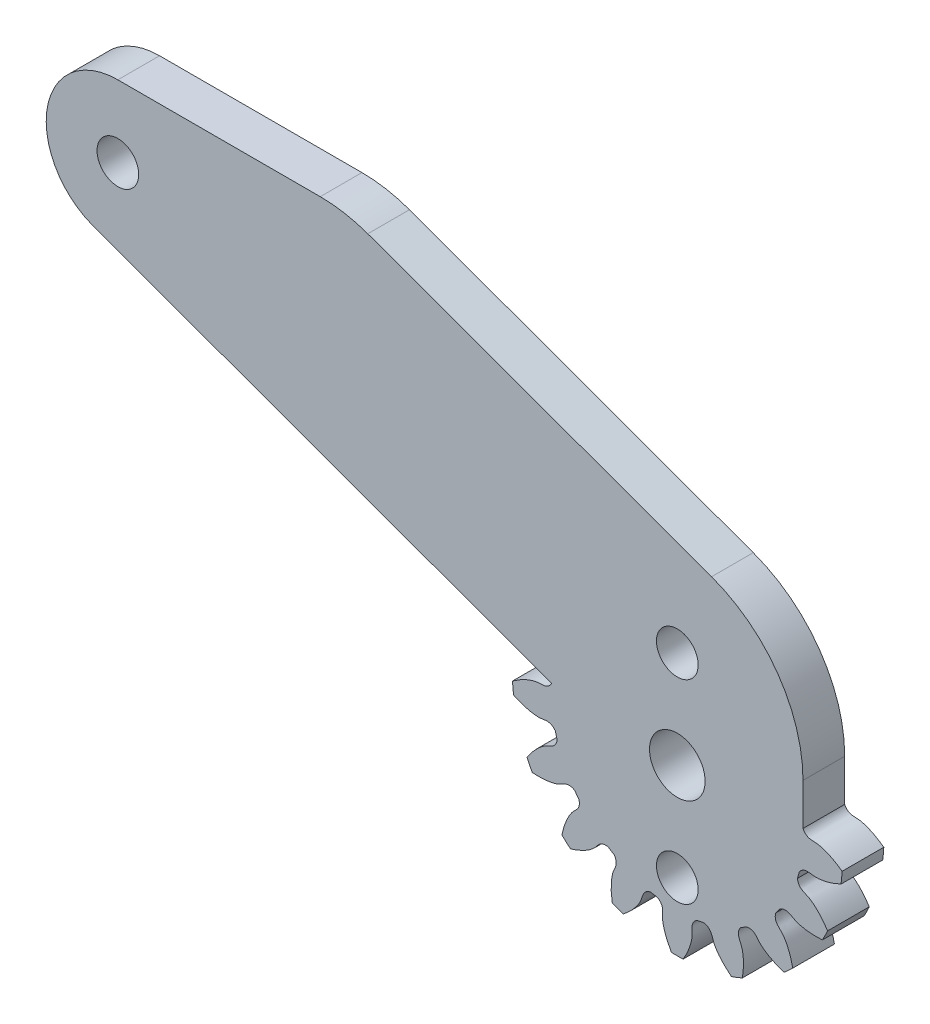
SolidWorks part; units mm, degrees
ref_plane "前视基准面" through (0, 0, 0) normal (0, 0, 1) x (1, 0, 0)
ref_plane "上视基准面" through (0, 0, 0) normal (0, 1, 0) x (1, 0, 0)
ref_plane "右视基准面" through (0, 0, 0) normal (1, 0, 0) x (0, 0, -1)
sketch "草图1" plane through (0, 0, 0) normal (0, 0, 1) x (1, 0, 0)
  circle A0 centre (0, 0) radius 11.875
extrude "凸台-拉伸1" add sketch "草图1" along normal blind 30
ref_axis "基准轴1" through (0, 0, -1.5) along (0, 0, 1)
sketch "草图2" plane through (0, 0, 0) normal (0, 0, 1) x (1, 0, 0)
  line L0 (0, 0) -> (0, 11.875) construction
  circle A0 centre (0, 0) radius 11.875 construction
  arc A1 (0.2521, 9.059) -> (-0.2521, 9.059) centre (0, 0) ccw
  arc A2 (3.8946, 13.4259) -> (-3.8946, 13.4259) centre (0, 0) ccw
  spline S0 degree 3 poles (0.2521, 9.059) (0.7848, 9.281) (0.7077, 9.6935) (0.7979, 10.081) (0.8062, 10.1139) (0.8163, 10.1505) (0.8282, 10.1907) (0.8421, 10.2345) (0.8582, 10.2818) (0.8766, 10.3324) (0.8974, 10.3865) (0.9208, 10.4438) (0.947, 10.5043) (0.976, 10.5679) (1.008, 10.6345) (1.0431, 10.704) (1.0815, 10.7763) (1.1232, 10.8513) (1.1685, 10.929) (1.2174, 11.0091) (1.27, 11.0916) (1.3265, 11.1763) (1.3869, 11.2632) (1.4514, 11.3521) (1.5201, 11.4429) (1.5931, 11.5354) (1.6704, 11.6295) (1.7522, 11.7251) (1.8386, 11.822) (1.9295, 11.9201) (2.0252, 12.0192) (2.1257, 12.1193) (2.2311, 12.22) (2.3414, 12.3213) (2.4567, 12.4231) (2.577, 12.5251) (2.7025, 12.6272) (2.8331, 12.7292) (2.969, 12.831) (3.1101, 12.9323) (3.2564, 13.0331) (3.4081, 13.1332) (3.6198, 13.2668) (3.7832, 13.3632) (3.8946, 13.4259) knots 0 0 0 0 0.193883 0.199024 0.204851 0.211363 0.21856 0.226443 0.235011 0.244265 0.254205 0.264829 0.27614 0.288136 0.300817 0.314184 0.328236 0.342973 0.358397 0.374505 0.391299 0.408779 0.426944 0.445795 0.465331 0.485552 0.506459 0.528051 0.550329 0.573293 0.596941 0.621276 0.646296 0.672001 0.698392 0.725468 0.753229 0.781677 0.810809 0.840627 0.871131 0.90232 0.934195 1 1 1 1
  spline S1 degree 3 poles (-0.2521, 9.059) (-0.7848, 9.281) (-0.7077, 9.6935) (-0.7979, 10.081) (-0.8062, 10.1139) (-0.8163, 10.1505) (-0.8282, 10.1907) (-0.8421, 10.2345) (-0.8582, 10.2818) (-0.8766, 10.3324) (-0.8974, 10.3865) (-0.9208, 10.4438) (-0.947, 10.5043) (-0.976, 10.5679) (-1.008, 10.6345) (-1.0431, 10.704) (-1.0815, 10.7763) (-1.1232, 10.8513) (-1.1685, 10.929) (-1.2174, 11.0091) (-1.27, 11.0916) (-1.3265, 11.1763) (-1.3869, 11.2632) (-1.4514, 11.3521) (-1.5201, 11.4429) (-1.5931, 11.5354) (-1.6704, 11.6295) (-1.7522, 11.7251) (-1.8386, 11.822) (-1.9295, 11.9201) (-2.0252, 12.0192) (-2.1257, 12.1193) (-2.2311, 12.22) (-2.3414, 12.3213) (-2.4567, 12.4231) (-2.577, 12.5251) (-2.7025, 12.6272) (-2.8331, 12.7292) (-2.969, 12.831) (-3.1101, 12.9323) (-3.2564, 13.0331) (-3.4081, 13.1332) (-3.6198, 13.2668) (-3.7832, 13.3632) (-3.8946, 13.4259) knots 0 0 0 0 0.193883 0.199024 0.204851 0.211363 0.21856 0.226443 0.235011 0.244265 0.254205 0.264829 0.27614 0.288136 0.300817 0.314184 0.328236 0.342973 0.358397 0.374505 0.391299 0.408779 0.426944 0.445795 0.465331 0.485552 0.506459 0.528051 0.550329 0.573293 0.596941 0.621276 0.646296 0.672001 0.698392 0.725468 0.753229 0.781677 0.810809 0.840627 0.871131 0.90232 0.934195 1 1 1 1
extrude "切除-拉伸1" cut sketch "草图2" along normal through all
pattern_circular "阵列(圆周)1" count 17 every 21.176 about axis through (0, 0, -1.5) along (0, 0, 1) of "切除-拉伸1"
sketch "草图3" plane through (0, 0, 0) normal (0, 0, 1) x (1, 0, 0)
  circle A0 centre (0, 0) radius 10.625 construction
  dimension "Dn" = 21.25
sketch "草图4" plane through (0, 0, 0) normal (0, 1, 0) x (1, 0, 0)
  line L1 (-14.2819, 27) -> (14.2819, 27)
  line L2 (-14.2819, 27) -> (-14.2819, -27)
  line L3 (-14.2819, -27) -> (14.2819, -27)
  line L4 (14.2819, 27) -> (14.2819, -27)
  line L5 (-14.2819, 27) -> (14.2819, -27) construction
  line L6 (-14.2819, -27) -> (14.2819, 27) construction
  point P0 (0, 0)
  dimension "D1" = 3
extrude "切除-拉伸2" cut sketch "草图4" against normal through all both and the other way through all
sketch "草图5" plane through (0, 0, 30) normal (0, 0, 1) x (1, 0, 0)
  arc A0 (8.9971, 1.0869) -> (-8.9971, 1.0869) centre (0, 0) ccw
  arc A34 (-3.0374, 8.5383) -> (-3.5076, 8.3562) centre (0, 0) ccw
  arc A35 (-5.8907, 10.3109) -> (-6.6043, 9.8691) centre (0, 0) ccw
  arc A36 (-5.9167, 6.8645) -> (-6.2893, 6.5248) centre (0, 0) ccw
  arc A37 (-9.2176, 7.4867) -> (-9.7234, 6.8169) centre (0, 0) ccw
  arc A38 (-7.9969, 4.2636) -> (-8.2217, 3.8123) centre (0, 0) ccw
  arc A39 (-11.2997, 3.6513) -> (-11.5294, 2.8441) centre (0, 0) ccw
  arc A40 (-8.9971, 1.0869) -> (-9.0436, 0.5848) centre (0, 0) ccw
  arc A41 (-11.8557, -0.6771) -> (-11.7782, -1.5129) centre (0, 0) ccw
  arc A42 (-8.7822, -2.2366) -> (-8.6442, -2.7216) centre (0, 0) ccw
  arc A43 (-10.8105, -4.9142) -> (-10.4364, -5.6655) centre (0, 0) ccw
  arc A44 (-7.3812, -5.2581) -> (-7.0773, -5.6605) centre (0, 0) ccw
  arc A45 (-8.3053, -8.4875) -> (-7.685, -9.053) centre (0, 0) ccw
  arc A46 (-4.9833, -7.5694) -> (-4.5546, -7.8348) centre (0, 0) ccw
  arc A47 (-4.6784, -10.9146) -> (-3.8958, -11.2178) centre (0, 0) ccw
  arc A48 (-1.9124, -8.8584) -> (-1.4168, -8.9511) centre (0, 0) ccw
  arc A49 (-0.4197, -11.8676) -> (0.4197, -11.8676) centre (0, 0) ccw
  arc A50 (1.4168, -8.9511) -> (1.9124, -8.8584) centre (0, 0) ccw
  arc A51 (3.8958, -11.2178) -> (4.6784, -10.9146) centre (0, 0) ccw
  arc A52 (4.5546, -7.8348) -> (4.9833, -7.5694) centre (0, 0) ccw
  arc A53 (7.685, -9.053) -> (8.3053, -8.4875) centre (0, 0) ccw
  arc A54 (7.0773, -5.6605) -> (7.3812, -5.2581) centre (0, 0) ccw
  arc A55 (10.4364, -5.6655) -> (10.8105, -4.9142) centre (0, 0) ccw
  arc A56 (8.6442, -2.7216) -> (8.7822, -2.2366) centre (0, 0) ccw
  arc A57 (11.7782, -1.5129) -> (11.8557, -0.6771) centre (0, 0) ccw
  arc A58 (9.0436, 0.5848) -> (8.9971, 1.0869) centre (0, 0) ccw
  arc A59 (11.5294, 2.8441) -> (11.2997, 3.6513) centre (0, 0) ccw
  arc A60 (8.2217, 3.8123) -> (7.9969, 4.2636) centre (0, 0) ccw
  arc A61 (9.7234, 6.8169) -> (9.2176, 7.4867) centre (0, 0) ccw
  arc A62 (6.2893, 6.5248) -> (5.9167, 6.8645) centre (0, 0) ccw
  arc A63 (6.6043, 9.8691) -> (5.8907, 10.3109) centre (0, 0) ccw
  arc A64 (3.5076, 8.3562) -> (3.0374, 8.5383) centre (0, 0) ccw
  arc A65 (2.5932, 11.5884) -> (1.7682, 11.7426) centre (0, 0) ccw
  arc A66 (0.2521, 9.059) -> (-0.2521, 9.059) centre (0, 0) ccw
  arc A67 (-1.7682, 11.7426) -> (-2.5932, 11.5884) centre (0, 0) ccw
  arc A68 (-3.0374, 8.5383) -> (-3.5076, 8.3562) centre (0, 0) ccw
  arc A69 (-5.8907, 10.3109) -> (-6.6043, 9.8691) centre (0, 0) ccw
  arc A70 (-5.9167, 6.8645) -> (-6.2893, 6.5248) centre (0, 0) ccw
  arc A71 (-9.2176, 7.4867) -> (-9.7234, 6.8169) centre (0, 0) ccw
  arc A72 (-7.9969, 4.2636) -> (-8.2217, 3.8123) centre (0, 0) ccw
  arc A73 (-11.2997, 3.6513) -> (-11.5294, 2.8441) centre (0, 0) ccw
  arc A93 (11.5294, 2.8441) -> (11.2997, 3.6513) centre (0, 0) ccw
  arc A94 (8.2217, 3.8123) -> (7.9969, 4.2636) centre (0, 0) ccw
  arc A95 (9.7234, 6.8169) -> (9.2176, 7.4867) centre (0, 0) ccw
  arc A96 (6.2893, 6.5248) -> (5.9167, 6.8645) centre (0, 0) ccw
  arc A97 (6.6043, 9.8691) -> (5.8907, 10.3109) centre (0, 0) ccw
  arc A98 (3.5076, 8.3562) -> (3.0374, 8.5383) centre (0, 0) ccw
  arc A99 (2.5932, 11.5884) -> (1.7682, 11.7426) centre (0, 0) ccw
  arc A100 (0.2521, 9.059) -> (-0.2521, 9.059) centre (0, 0) ccw
  arc A101 (-1.7682, 11.7426) -> (-2.5932, 11.5884) centre (0, 0) ccw
  spline S34 degree 3 poles (3204.5235, 2397.2936) (-37.2918, -28.382) (-0.6945, 3.695) (-4.3928, 9.1225) (-4.43, 9.1736) (-4.4845, 9.2426) (-4.5521, 9.3214) (-4.6337, 9.4092) (-4.73, 9.505) (-4.8419, 9.6076) (-4.9699, 9.716) (-5.1147, 9.8291) (-5.277, 9.9456) (-5.4571, 10.0643) (-28.9545, 24.2415) (-145.9515, -123.9226) (3580.2885, 1781.0225) knots -2.702617 -2.702617 -2.702617 -2.702617 0.661536 0.666677 0.679016 0.694096 0.711918 0.732483 0.755789 0.781837 0.810627 0.842158 0.876432 0.913448 0.953205 15.004551 15.004551 15.004551 15.004551 only from (-3.5076, 8.3562) to (-5.8907, 10.3109)
  spline S35 degree 3 poles (-3190.1071, -2411.2489) (175.7802, 75.3751) (-8.7927, 36.7085) (-6.5767, 9.371) (-6.5507, 9.1569) (-6.5188, 8.9597) (-6.4821, 8.7797) (-6.4422, 8.6167) (-6.4001, 8.4709) (-6.3574, 8.342) (-6.3151, 8.2298) (-6.2747, 8.1342) (-6.2373, 8.0546) (-6.2081, 7.9985) (-2.9981, 2.2687) (42.0277, 20.7308) (-3574.1983, -1799.9306) knots -13.996313 -13.996313 -13.996313 -13.996313 0.046795 0.086552 0.123568 0.157842 0.189373 0.218163 0.244211 0.267517 0.288082 0.305904 0.320984 0.333323 0.338464 3.702571 3.702571 3.702571 3.702571 only from (-6.6043, 9.8691) to (-5.9167, 6.8645)
  spline S36 degree 3 poles (2122.1269, 3393.0171) (-24.5208, -39.9368) (-1.9823, 3.1946) (-7.3916, 6.9196) (-7.4448, 6.9538) (-7.5205, 6.9984) (-7.612, 7.0475) (-7.7198, 7.0999) (-7.8442, 7.1544) (-7.9856, 7.2097) (-8.1441, 7.2646) (-8.32, 7.3177) (-8.5134, 7.3677) (-8.7242, 7.4133) (-35.7563, 12.145) (-91.3297, -168.2782) (2695.1401, 2954.1034) knots -2.702617 -2.702617 -2.702617 -2.702617 0.661536 0.666677 0.679016 0.694096 0.711918 0.732483 0.755789 0.781837 0.810627 0.842158 0.876432 0.913448 0.953205 15.004551 15.004551 15.004551 15.004551 only from (-6.2893, 6.5248) to (-9.2176, 7.4867)
  spline S37 degree 3 poles (-2103.6427, -3400.8222) (136.6815, 133.7844) (-21.4596, 31.0533) (-9.5178, 6.3624) (-9.4162, 6.1721) (-9.3152, 5.9998) (-9.216, 5.8452) (-9.1199, 5.7077) (-9.028, 5.5869) (-8.9415, 5.4821) (-8.8616, 5.3928) (-8.7894, 5.3182) (-8.7257, 5.2576) (-8.6783, 5.2158) (-3.6152, 1.0325) (31.7008, 34.5131) (-2682.6307, -2969.5347) knots -13.996313 -13.996313 -13.996313 -13.996313 0.046795 0.086552 0.123568 0.157842 0.189373 0.218163 0.244211 0.267517 0.288082 0.305904 0.320984 0.333323 0.338464 3.702571 3.702571 3.702571 3.702571 only from (-9.7234, 6.8169) to (-7.9969, 4.2636)
  spline S38 degree 3 poles (753.1252, 3930.4949) (-8.4382, -46.0979) (-3.0025, 2.2628) (-9.3921, 3.7822) (-9.4541, 3.7949) (-9.5408, 3.8091) (-9.6439, 3.8218) (-9.7633, 3.8318) (-9.899, 3.8377) (-10.0508, 3.8382) (-10.2184, 3.832) (-10.4016, 3.818) (-10.6, 3.7948) (-10.8131, 3.7612) (-37.7291, -1.5918) (-24.3733, -189.9068) (1445.998, 3728.2163) knots -2.702617 -2.702617 -2.702617 -2.702617 0.661536 0.666677 0.679016 0.694096 0.711918 0.732483 0.755789 0.781837 0.810627 0.842158 0.876432 0.913448 0.953205 15.004551 15.004551 15.004551 15.004551 only from (-8.2217, 3.8123) to (-11.2997, 3.6513)
  spline S39 degree 3 poles (-733.0697, -3931.0957) (79.1232, 174.1253) (-31.2282, 21.2042) (-11.1735, 2.4945) (-11.01, 2.3538) (-10.8536, 2.2296) (-10.7052, 2.1213) (-10.5659, 2.0278) (-10.4365, 1.9483) (-10.3181, 1.8819) (-10.2113, 1.8274) (-10.117, 1.784) (-10.0358, 1.7504) (-9.9764, 1.7286) (-3.7441, -0.3432) (17.0926, 43.6341) (-1428.759, -3738.0866) knots -13.996313 -13.996313 -13.996313 -13.996313 0.046795 0.086552 0.123568 0.157842 0.189373 0.218163 0.244211 0.267517 0.288082 0.305904 0.320984 0.333323 0.338464 3.702571 3.702571 3.702571 3.702571 only from (-11.5294, 2.8441) to (-8.9971, 1.0869)
  spline S40 degree 3 poles (-180.8455, 985.7124) (0.5211, -18.0724) (-5.9831, 0.7012) (-10.1242, 0.134) (-10.1865, 0.1234) (-10.2725, 0.1054) (-10.3733, 0.08) (-10.4882, 0.0461) (-10.6168, 0.0026) (-10.7586, -0.0518) (-10.9127, -0.1181) (-11.0784, -0.1973) (-11.255, -0.2906) (-11.4416, -0.3989) (-26.4837, -9.954) (2.0889, -85.1042) (11.954, 999.039) knots -1.473067 -1.473067 -1.473067 -1.473067 0.661536 0.666677 0.679016 0.694096 0.711918 0.732483 0.755789 0.781837 0.810627 0.842158 0.876432 0.913448 0.953205 10.050586 10.050586 10.050586 10.050586 only from (-9.0436, 0.5848) to (-11.8557, -0.6771)
  spline S41 degree 3 poles (195.3333, -979.8293) (-13.603, 83.9465) (-27.8517, 4.9141) (-11.3201, -1.7102) (-11.1168, -1.7824) (-10.9261, -1.8417) (-10.7486, -1.8891) (-10.5849, -1.926) (-10.4356, -1.9534) (-10.3011, -1.9725) (-10.1819, -1.9847) (-10.0783, -1.9911) (-9.9904, -1.9931) (-9.9272, -1.992) (-5.7524, -1.7887) (-2.8087, 17.8598) (3.3576, -1002.1119) knots -9.044973 -9.044973 -9.044973 -9.044973 0.046795 0.086552 0.123568 0.157842 0.189373 0.218163 0.244211 0.267517 0.288082 0.305904 0.320984 0.333323 0.338464 2.473034 2.473034 2.473034 2.473034 only from (-11.7782, -1.5129) to (-8.7822, -2.2366)
  spline S42 degree 3 poles (-524.7138, 853.8205) (7.0144, -16.6638) (-5.8324, -1.5074) (-9.4889, -3.5324) (-9.5433, -3.5647) (-9.6169, -3.6126) (-9.7017, -3.6727) (-9.7966, -3.7458) (-9.9008, -3.8328) (-10.0134, -3.9347) (-10.1331, -4.0522) (-10.2591, -4.186) (-10.39, -4.3368) (-10.5249, -4.5052) (-21.0995, -18.8488) (32.691, -78.6027) (-349.7478, 935.8944) knots -1.473067 -1.473067 -1.473067 -1.473067 0.661536 0.666677 0.679016 0.694096 0.711918 0.732483 0.755789 0.781837 0.810627 0.842158 0.876432 0.913448 0.953205 10.050586 10.050586 10.050586 10.050586 only from (-8.6442, -2.7216) to (-10.8105, -4.9142)
  spline S43 degree 3 poles (536.0981, -843.1011) (-43.0094, 73.3638) (-27.7461, -5.479) (-9.9378, -5.684) (-9.7222, -5.6779) (-9.523, -5.6643) (-9.3403, -5.6444) (-9.1744, -5.6196) (-9.0253, -5.5912) (-8.893, -5.5605) (-8.7774, -5.5288) (-8.6784, -5.4974) (-8.5958, -5.4675) (-8.5372, -5.4436) (-4.7178, -3.7459) (-9.0707, 15.6392) (365.1354, -933.2286) knots -9.044973 -9.044973 -9.044973 -9.044973 0.046795 0.086552 0.123568 0.157842 0.189373 0.218163 0.244211 0.267517 0.288082 0.305904 0.320984 0.333323 0.338464 2.473034 2.473034 2.473034 2.473034 only from (-10.4364, -5.6655) to (-7.3812, -5.2581)
  spline S44 degree 3 poles (-797.7166, 606.6154) (12.5604, -13.0046) (-4.894, -3.5126) (-7.5721, -6.7216) (-7.6111, -6.7714) (-7.6625, -6.8427) (-7.7198, -6.9293) (-7.7819, -7.0318) (-7.8477, -7.1506) (-7.9158, -7.2863) (-7.985, -7.4391) (-8.0541, -7.6093) (-8.1218, -7.7973) (-8.1867, -8.003) (-12.8657, -25.198) (58.878, -61.4855) (-664.2141, 746.3521) knots -1.473067 -1.473067 -1.473067 -1.473067 0.661536 0.666677 0.679016 0.694096 0.711918 0.732483 0.755789 0.781837 0.810627 0.842158 0.876432 0.913448 0.953205 10.050586 10.050586 10.050586 10.050586 only from (-7.0773, -5.6605) to (-8.3053, -8.4875)
  spline S45 degree 3 poles (804.4598, -592.5074) (-66.6071, 52.8729) (-23.8932, -15.132) (-7.2135, -8.8902) (-7.0146, -8.8066) (-6.8337, -8.7219) (-6.6706, -8.6374) (-6.5248, -8.5543) (-6.396, -8.474) (-6.2837, -8.3976) (-6.1874, -8.3262) (-6.1065, -8.2612) (-6.0403, -8.2034) (-5.9943, -8.16) (-3.0461, -5.1973) (-14.1077, 11.3064) (677.5997, -738.3076) knots -9.044973 -9.044973 -9.044973 -9.044973 0.046795 0.086552 0.123568 0.157842 0.189373 0.218163 0.244211 0.267517 0.288082 0.305904 0.320984 0.333323 0.338464 2.473034 2.473034 2.473034 2.473034 only from (-7.685, -9.053) to (-4.9833, -7.5694)
  spline S46 degree 3 poles (-962.9834, 277.4835) (16.41, -7.5891) (-3.2946, -5.0433) (-4.6327, -9.0031) (-4.651, -9.0636) (-4.6732, -9.1486) (-4.6954, -9.2501) (-4.7163, -9.3681) (-4.7346, -9.5027) (-4.7492, -9.6538) (-4.7585, -9.8213) (-4.7614, -10.005) (-4.7566, -10.2046) (-4.7428, -10.4199) (-2.8943, -28.1441) (77.1132, -36.0643) (-888.9747, 456.0108) knots -1.473067 -1.473067 -1.473067 -1.473067 0.661536 0.666677 0.679016 0.694096 0.711918 0.732483 0.755789 0.781837 0.810627 0.842158 0.876432 0.913448 0.953205 10.050586 10.050586 10.050586 10.050586 only from (-4.5546, -7.8348) to (-4.6784, -10.9146)
  spline S47 degree 3 poles (964.1748, -261.8923) (-81.2092, 25.2412) (-16.8134, -22.7414) (-3.5148, -10.8956) (-3.3596, -10.7459) (-3.2216, -10.6015) (-3.1, -10.4638) (-2.994, -10.3337) (-2.903, -10.2123) (-2.8259, -10.1004) (-2.7618, -9.9992) (-2.7099, -9.9092) (-2.669, -9.8315) (-2.6418, -9.7744) (-0.9629, -5.9467) (-17.2394, 5.4466) (898.5504, -443.6741) knots -9.044973 -9.044973 -9.044973 -9.044973 0.046795 0.086552 0.123568 0.157842 0.189373 0.218163 0.244211 0.267517 0.288082 0.305904 0.320984 0.333323 0.338464 2.473034 2.473034 2.473034 2.473034 only from (-3.8958, -11.2178) to (-1.9124, -8.8584)
  spline S48 degree 3 poles (-998.1939, -89.124) (18.0434, -1.1487) (-1.2503, -5.8929) (-1.0675, -10.0686) (-1.0628, -10.1317) (-1.0527, -10.219) (-1.0368, -10.3216) (-1.0137, -10.4392) (-0.9822, -10.5713) (-0.9411, -10.7174) (-0.8893, -10.877) (-0.8257, -11.0494) (-0.7491, -11.2338) (-0.6585, -11.4296) (7.4679, -27.2891) (84.9339, -5.7725) (-993.6743, 104.0827) knots -1.473067 -1.473067 -1.473067 -1.473067 0.661536 0.666677 0.679016 0.694096 0.711918 0.732483 0.755789 0.781837 0.810627 0.842158 0.876432 0.913448 0.953205 10.050586 10.050586 10.050586 10.050586 only from (-1.4168, -8.9511) to (-0.4197, -11.8676)
  spline S49 degree 3 poles (993.6726, 104.0928) (-84.8435, -5.7994) (-7.4629, -27.2794) (0.6585, -11.4296) (0.7491, -11.2338) (0.8257, -11.0494) (0.8893, -10.877) (0.9411, -10.7174) (0.9822, -10.5713) (1.0137, -10.4392) (1.0368, -10.3216) (1.0527, -10.219) (1.0628, -10.1317) (1.0675, -10.0686) (1.2503, -5.8929) (-18.0428, -1.1488) (998.1469, -89.1199) knots -9.044973 -9.044973 -9.044973 -9.044973 0.046795 0.086552 0.123568 0.157842 0.189373 0.218163 0.244211 0.267517 0.288082 0.305904 0.320984 0.333323 0.338464 2.473034 2.473034 2.473034 2.473034 only from (0.4197, -11.8676) to (1.4168, -8.9511)
  spline S50 degree 3 poles (-898.5927, -443.6949) (17.2399, 5.4469) (0.9629, -5.9466) (2.6418, -9.7744) (2.669, -9.8315) (2.7099, -9.9092) (2.7618, -9.9992) (2.8259, -10.1004) (2.903, -10.2123) (2.994, -10.3337) (3.1, -10.4638) (3.2216, -10.6015) (3.3596, -10.7459) (3.5148, -10.8956) (16.8216, -22.7486) (81.2838, 25.299) (-964.1727, -261.9023) knots -1.473067 -1.473067 -1.473067 -1.473067 0.661536 0.666677 0.679016 0.694096 0.711918 0.732483 0.755789 0.781837 0.810627 0.842158 0.876432 0.913448 0.953205 10.050586 10.050586 10.050586 10.050586 only from (1.9124, -8.8584) to (3.8958, -11.2178)
  spline S51 degree 3 poles (888.9695, 456.0196) (-77.0192, -36.0568) (2.8955, -28.1332) (4.7428, -10.4199) (4.7566, -10.2046) (4.7614, -10.005) (4.7585, -9.8213) (4.7492, -9.6538) (4.7346, -9.5027) (4.7163, -9.3681) (4.6954, -9.2501) (4.6732, -9.1486) (4.651, -9.0636) (4.6327, -9.0031) (3.2946, -5.0433) (-16.4094, -7.589) (962.9381, 277.4704) knots -9.044973 -9.044973 -9.044973 -9.044973 0.046795 0.086552 0.123568 0.157842 0.189373 0.218163 0.244211 0.267517 0.288082 0.305904 0.320984 0.333323 0.338464 2.473034 2.473034 2.473034 2.473034 only from (4.6784, -10.9146) to (4.5546, -7.8348)
  spline S52 degree 3 poles (-677.6317, -738.3423) (14.1081, 11.3069) (3.046, -5.1972) (5.9943, -8.16) (6.0403, -8.2034) (6.1065, -8.2612) (6.1874, -8.3262) (6.2837, -8.3976) (6.396, -8.474) (6.5248, -8.5543) (6.6706, -8.6374) (6.8337, -8.7219) (7.0146, -8.8066) (7.2135, -8.8902) (23.9034, -15.1358) (66.6558, 52.9537) (-804.4542, -592.516) knots -1.473067 -1.473067 -1.473067 -1.473067 0.661536 0.666677 0.679016 0.694096 0.711918 0.732483 0.755789 0.781837 0.810627 0.842158 0.876432 0.913448 0.953205 10.050586 10.050586 10.050586 10.050586 only from (4.9833, -7.5694) to (7.685, -9.053)
  spline S53 degree 3 poles (664.2061, 746.3584) (-58.7931, -61.4445) (12.8629, -25.1875) (8.1867, -8.003) (8.1218, -7.7973) (8.0541, -7.6093) (7.985, -7.4391) (7.9158, -7.2863) (7.8477, -7.1506) (7.7819, -7.0318) (7.7198, -6.9293) (7.6625, -6.8427) (7.6111, -6.7714) (7.5721, -6.7216) (4.894, -3.5126) (-12.5599, -13.0043) (797.6792, 606.5868) knots -9.044973 -9.044973 -9.044973 -9.044973 0.046795 0.086552 0.123568 0.157842 0.189373 0.218163 0.244211 0.267517 0.288082 0.305904 0.320984 0.333323 0.338464 2.473034 2.473034 2.473034 2.473034 only from (8.3053, -8.4875) to (7.0773, -5.6605)
  spline S54 degree 3 poles (-365.1527, -933.2725) (9.0709, 15.6398) (4.7178, -3.7459) (8.5372, -5.4436) (8.5958, -5.4675) (8.6784, -5.4974) (8.7774, -5.5288) (8.893, -5.5605) (9.0253, -5.5912) (9.1744, -5.6196) (9.3403, -5.6444) (9.523, -5.6643) (9.7222, -5.6779) (9.9378, -5.684) (27.757, -5.4788) (43.0256, 73.4567) (-536.0897, -843.1071) knots -1.473067 -1.473067 -1.473067 -1.473067 0.661536 0.666677 0.679016 0.694096 0.711918 0.732483 0.755789 0.781837 0.810627 0.842158 0.876432 0.913448 0.953205 10.050586 10.050586 10.050586 10.050586 only from (7.3812, -5.2581) to (10.4364, -5.6655)
  spline S55 degree 3 poles (349.7379, 935.8974) (-32.6266, -78.5338) (21.093, -18.84) (10.5249, -4.5052) (10.39, -4.3368) (10.2591, -4.186) (10.1331, -4.0522) (10.0134, -3.9347) (9.9008, -3.8328) (9.7966, -3.7458) (9.7017, -3.6727) (9.6169, -3.6126) (9.5433, -3.5647) (9.4889, -3.5324) (5.8324, -1.5075) (-7.014, -16.6633) (524.6893, 853.7803) knots -9.044973 -9.044973 -9.044973 -9.044973 0.046795 0.086552 0.123568 0.157842 0.189373 0.218163 0.244211 0.267517 0.288082 0.305904 0.320984 0.333323 0.338464 2.473034 2.473034 2.473034 2.473034 only from (10.8105, -4.9142) to (8.6442, -2.7216)
  spline S56 degree 3 poles (-3.3579, -1002.1591) (2.8086, 17.8605) (5.7524, -1.7887) (9.9272, -1.992) (9.9904, -1.9931) (10.0783, -1.9911) (10.1819, -1.9847) (10.3011, -1.9725) (10.4356, -1.9534) (10.5849, -1.926) (10.7486, -1.8891) (10.9261, -1.8417) (11.1168, -1.7824) (11.3201, -1.7102) (27.8618, 4.9181) (13.5846, 84.039) (-195.3234, -979.8319) knots -1.473067 -1.473067 -1.473067 -1.473067 0.661536 0.666677 0.679016 0.694096 0.711918 0.732483 0.755789 0.781837 0.810627 0.842158 0.876432 0.913448 0.953205 10.050586 10.050586 10.050586 10.050586 only from (8.7822, -2.2366) to (11.7782, -1.5129)
  spline S57 degree 3 poles (-11.9642, 999.0383) (-2.0537, -85.0167) (26.4745, -9.9481) (11.4416, -0.3989) (11.255, -0.2906) (11.0784, -0.1973) (10.9127, -0.1181) (10.7586, -0.0518) (10.6168, 0.0026) (10.4882, 0.0461) (10.3733, 0.08) (10.2725, 0.1054) (10.1865, 0.1234) (10.1242, 0.134) (5.9832, 0.7012) (-0.5209, -18.0718) (180.8372, 985.666) knots -9.044973 -9.044973 -9.044973 -9.044973 0.046795 0.086552 0.123568 0.157842 0.189373 0.218163 0.244211 0.267517 0.288082 0.305904 0.320984 0.333323 0.338464 2.473034 2.473034 2.473034 2.473034 only from (11.8557, -0.6771) to (9.0436, 0.5848)
  spline S58 degree 3 poles (1428.8189, -3738.2434) (-17.0931, 43.6354) (3.744, -0.3432) (9.9764, 1.7286) (10.0358, 1.7504) (10.117, 1.784) (10.2113, 1.8274) (10.3181, 1.8819) (10.4365, 1.9483) (10.5659, 2.0278) (10.7052, 2.1213) (10.8536, 2.2296) (11.01, 2.3538) (11.1735, 2.4945) (31.2399, 21.2152) (-79.2504, 174.293) (733.2407, -3931.0132) knots -2.702617 -2.702617 -2.702617 -2.702617 0.661536 0.666677 0.679016 0.694096 0.711918 0.732483 0.755789 0.781837 0.810627 0.842158 0.876432 0.913448 0.953205 15.004551 15.004551 15.004551 15.004551 only from (8.9971, 1.0869) to (11.5294, 2.8441)
  spline S59 degree 3 poles (-1446.1867, 3728.1964) (24.3932, -189.6973) (37.7134, -1.5887) (10.8131, 3.7612) (10.6, 3.7948) (10.4016, 3.818) (10.2184, 3.832) (10.0508, 3.8382) (9.899, 3.8377) (9.7633, 3.8318) (9.6439, 3.8218) (9.5408, 3.8091) (9.4541, 3.7949) (9.3921, 3.7822) (3.0026, 2.2628) (8.438, -46.0966) (-753.0937, 3930.3299) knots -13.996313 -13.996313 -13.996313 -13.996313 0.046795 0.086552 0.123568 0.157842 0.189373 0.218163 0.244211 0.267517 0.288082 0.305904 0.320984 0.333323 0.338464 3.702571 3.702571 3.702571 3.702571 only from (11.2997, 3.6513) to (8.2217, 3.8123)
  spline S60 degree 3 poles (2682.7433, -2969.6593) (-31.7018, 34.514) (3.6152, 1.0324) (8.6783, 5.2158) (8.7257, 5.2576) (8.7894, 5.3182) (8.8616, 5.3928) (8.9415, 5.4821) (9.028, 5.5869) (9.1199, 5.7077) (9.216, 5.8452) (9.3152, 5.9998) (9.4162, 6.1721) (9.5178, 6.3624) (21.4666, 31.0677) (-136.8607, 133.8948) (2103.7723, -3400.6836) knots -2.702617 -2.702617 -2.702617 -2.702617 0.661536 0.666677 0.679016 0.694096 0.711918 0.732483 0.755789 0.781837 0.810627 0.842158 0.876432 0.913448 0.953205 15.004551 15.004551 15.004551 15.004551 only from (7.9969, 4.2636) to (9.7234, 6.8169)
  spline S61 degree 3 poles (-2695.3088, 2954.0167) (91.2726, -168.0756) (35.7406, 12.1422) (8.7242, 7.4133) (8.5134, 7.3677) (8.32, 7.3177) (8.1441, 7.2646) (7.9856, 7.2097) (7.8442, 7.1544) (7.7198, 7.0999) (7.612, 7.0475) (7.5205, 6.9984) (7.4448, 6.9538) (7.3916, 6.9196) (1.9824, 3.1947) (24.5202, -39.9356) (-2122.0379, 3392.8747) knots -13.996313 -13.996313 -13.996313 -13.996313 0.046795 0.086552 0.123568 0.157842 0.189373 0.218163 0.244211 0.267517 0.288082 0.305904 0.320984 0.333323 0.338464 3.702571 3.702571 3.702571 3.702571 only from (9.2176, 7.4867) to (6.2893, 6.5248)
  spline S62 degree 3 poles (3574.3482, -1800.0062) (-42.0289, 20.7313) (2.9981, 2.2687) (6.2081, 7.9985) (6.2373, 8.0546) (6.2747, 8.1342) (6.3151, 8.2298) (6.3574, 8.342) (6.4001, 8.4709) (6.4422, 8.6167) (6.4821, 8.7797) (6.5188, 8.9597) (6.5507, 9.1569) (6.5767, 9.371) (8.794, 36.7244) (-175.9872, 75.4134) (3190.1779, -2411.0728) knots -2.702617 -2.702617 -2.702617 -2.702617 0.661536 0.666677 0.679016 0.694096 0.711918 0.732483 0.755789 0.781837 0.810627 0.842158 0.876432 0.913448 0.953205 15.004551 15.004551 15.004551 15.004551 only from (5.9167, 6.8645) to (6.6043, 9.8691)
  spline S63 degree 3 poles (-3580.4146, 1780.8806) (145.825, -123.7544) (28.9408, 24.2333) (5.4571, 10.0643) (5.277, 9.9456) (5.1147, 9.8291) (4.9699, 9.716) (4.8419, 9.6076) (4.73, 9.505) (4.6337, 9.4092) (4.5521, 9.3214) (4.4845, 9.2426) (4.43, 9.1736) (4.3928, 9.1225) (0.6945, 3.6951) (37.2908, -28.3811) (-3204.3891, 2397.193) knots -13.996313 -13.996313 -13.996313 -13.996313 0.046795 0.086552 0.123568 0.157842 0.189373 0.218163 0.244211 0.267517 0.288082 0.305904 0.320984 0.333323 0.338464 3.702571 3.702571 3.702571 3.702571 only from (5.8907, 10.3109) to (3.5076, 8.3562)
  spline S64 degree 3 poles (3983.2177, -387.2522) (-46.6798, 4.1488) (1.9761, 3.1985) (2.8995, 9.701) (2.9064, 9.7639) (2.9126, 9.8516) (2.9157, 9.9554) (2.9146, 10.0752) (2.9079, 10.2108) (2.8944, 10.362) (2.8728, 10.5284) (2.842, 10.7095) (2.8005, 10.9049) (2.7474, 11.114) (-5.0662, 37.4213) (-191.3456, 6.747) (3845.7322, -1095.8333) knots -2.702617 -2.702617 -2.702617 -2.702617 0.661536 0.666677 0.679016 0.694096 0.711918 0.732483 0.755789 0.781837 0.810627 0.842158 0.876432 0.913448 0.953205 15.004551 15.004551 15.004551 15.004551 only from (3.0374, 8.5383) to (2.5932, 11.5884)
  spline S65 degree 3 poles (-3981.9654, 367.2268) (180.683, -62.7194) (18.2324, 33.0515) (1.4529, 11.356) (1.3279, 11.1802) (1.2187, 11.013) (1.1245, 10.8552) (1.0442, 10.7079) (0.977, 10.5718) (0.9218, 10.4477) (0.8775, 10.3364) (0.8429, 10.2384) (0.817, 10.1545) (0.8007, 10.0933) (-0.6872, 3.6964) (45.0251, -12.9936) (-3853.9698, 1077.757) knots -13.996313 -13.996313 -13.996313 -13.996313 0.046795 0.086552 0.123568 0.157842 0.189373 0.218163 0.244211 0.267517 0.288082 0.305904 0.320984 0.333323 0.338464 3.702571 3.702571 3.702571 3.702571 only from (1.7682, 11.7426) to (0.2521, 9.059)
  spline S66 degree 3 poles (3854.1315, 1077.8022) (-45.0264, -12.9941) (0.6872, 3.6964) (-0.8007, 10.0933) (-0.817, 10.1545) (-0.8429, 10.2384) (-0.8775, 10.3364) (-0.9218, 10.4477) (-0.977, 10.5718) (-1.0442, 10.7079) (-1.1245, 10.8552) (-1.2187, 11.013) (-1.3279, 11.1802) (-1.4529, 11.356) (-18.2422, 33.0642) (-180.8618, -62.8306) (3981.8991, 367.4046) knots -2.702617 -2.702617 -2.702617 -2.702617 0.661536 0.666677 0.679016 0.694096 0.711918 0.732483 0.755789 0.781837 0.810627 0.842158 0.876432 0.913448 0.953205 15.004551 15.004551 15.004551 15.004551 only from (-0.2521, 9.059) to (-1.7682, 11.7426)
  spline S67 degree 3 poles (-3845.7298, -1096.023) (191.1388, 6.7861) (5.0616, 37.4059) (-2.7474, 11.114) (-2.8005, 10.9049) (-2.842, 10.7095) (-2.8728, 10.5284) (-2.8944, 10.362) (-2.9079, 10.2108) (-2.9146, 10.0752) (-2.9157, 9.9554) (-2.9126, 9.8516) (-2.9064, 9.7639) (-2.8995, 9.701) (-1.9761, 3.1986) (46.6785, 4.1488) (-3983.0506, -387.236) knots -13.996313 -13.996313 -13.996313 -13.996313 0.046795 0.086552 0.123568 0.157842 0.189373 0.218163 0.244211 0.267517 0.288082 0.305904 0.320984 0.333323 0.338464 3.702571 3.702571 3.702571 3.702571 only from (-2.5932, 11.5884) to (-3.0374, 8.5383)
  spline S68 degree 3 poles (-3.5076, 8.3562) (-4.0845, 8.3708) (-4.1617, 8.7833) (-4.3928, 9.1225) (-4.43, 9.1736) (-4.4845, 9.2426) (-4.5521, 9.3214) (-4.6337, 9.4092) (-4.73, 9.505) (-4.8419, 9.6076) (-4.9699, 9.716) (-5.1147, 9.8291) (-5.277, 9.9456) (-5.4571, 10.0643) (-5.6626, 10.1883) (-5.8101, 10.269) (-5.8907, 10.3109) knots 0.467653 0.467653 0.467653 0.467653 0.661536 0.666677 0.679016 0.694096 0.711918 0.732483 0.755789 0.781837 0.810627 0.842158 0.876432 0.913448 0.953205 1 1 1 1
  spline S69 degree 3 poles (-6.6043, 9.8691) (-6.6027, 9.7782) (-6.5961, 9.6102) (-6.5767, 9.371) (-6.5507, 9.1569) (-6.5188, 8.9597) (-6.4821, 8.7797) (-6.4422, 8.6167) (-6.4001, 8.4709) (-6.3574, 8.342) (-6.3151, 8.2298) (-6.2747, 8.1342) (-6.2373, 8.0546) (-6.2081, 7.9985) (-6.0075, 7.6404) (-5.6726, 7.3875) (-5.9167, 6.8645) knots 0 0 0 0 0.046795 0.086552 0.123568 0.157842 0.189373 0.218163 0.244211 0.267517 0.288082 0.305904 0.320984 0.333323 0.338464 0.532347 0.532347 0.532347 0.532347
  spline S70 degree 3 poles (-6.2893, 6.5248) (-6.8326, 6.33) (-7.0535, 6.6868) (-7.3916, 6.9196) (-7.4448, 6.9538) (-7.5205, 6.9984) (-7.612, 7.0475) (-7.7198, 7.0999) (-7.8442, 7.1544) (-7.9856, 7.2097) (-8.1441, 7.2646) (-8.32, 7.3177) (-8.5134, 7.3677) (-8.7242, 7.4133) (-8.9606, 7.4547) (-9.1273, 7.4767) (-9.2176, 7.4867) knots 0.467653 0.467653 0.467653 0.467653 0.661536 0.666677 0.679016 0.694096 0.711918 0.732483 0.755789 0.781837 0.810627 0.842158 0.876432 0.913448 0.953205 1 1 1 1
  spline S71 degree 3 poles (-9.7234, 6.8169) (-9.6891, 6.7328) (-9.6223, 6.5785) (-9.5178, 6.3624) (-9.4162, 6.1721) (-9.3152, 5.9998) (-9.216, 5.8452) (-9.1199, 5.7077) (-9.028, 5.5869) (-8.9415, 5.4821) (-8.8616, 5.3928) (-8.7894, 5.3182) (-8.7257, 5.2576) (-8.6783, 5.2158) (-8.3618, 4.9543) (-7.9582, 4.8395) (-7.9969, 4.2636) knots 0 0 0 0 0.046795 0.086552 0.123568 0.157842 0.189373 0.218163 0.244211 0.267517 0.288082 0.305904 0.320984 0.333323 0.338464 0.532347 0.532347 0.532347 0.532347
  spline S72 degree 3 poles (-8.2217, 3.8123) (-8.6579, 3.4343) (-8.9927, 3.6872) (-9.3921, 3.7822) (-9.4541, 3.7949) (-9.5408, 3.8091) (-9.6439, 3.8218) (-9.7633, 3.8318) (-9.899, 3.8377) (-10.0508, 3.8382) (-10.2184, 3.832) (-10.4016, 3.818) (-10.6, 3.7948) (-10.8131, 3.7612) (-11.0485, 3.7144) (-11.2119, 3.6747) (-11.2997, 3.6513) knots 0.467653 0.467653 0.467653 0.467653 0.661536 0.666677 0.679016 0.694096 0.711918 0.732483 0.755789 0.781837 0.810627 0.842158 0.876432 0.913448 0.953205 1 1 1 1
  spline S73 degree 3 poles (-11.5294, 2.8441) (-11.467, 2.778) (-11.349, 2.6583) (-11.1735, 2.4945) (-11.01, 2.3538) (-10.8536, 2.2296) (-10.7052, 2.1213) (-10.5659, 2.0278) (-10.4365, 1.9483) (-10.3181, 1.8819) (-10.2113, 1.8274) (-10.117, 1.784) (-10.0358, 1.7504) (-9.9764, 1.7286) (-9.5869, 1.5991) (-9.169, 1.6378) (-8.9971, 1.0869) knots 0 0 0 0 0.046795 0.086552 0.123568 0.157842 0.189373 0.218163 0.244211 0.267517 0.288082 0.305904 0.320984 0.333323 0.338464 0.532347 0.532347 0.532347 0.532347
  spline S92 degree 3 poles (8.9971, 1.0869) (9.169, 1.6378) (9.5869, 1.5991) (9.9764, 1.7286) (10.0358, 1.7504) (10.117, 1.784) (10.2113, 1.8274) (10.3181, 1.8819) (10.4365, 1.9483) (10.5659, 2.0278) (10.7052, 2.1213) (10.8536, 2.2296) (11.01, 2.3538) (11.1735, 2.4945) (11.349, 2.6583) (11.467, 2.778) (11.5294, 2.8441) knots 0.467653 0.467653 0.467653 0.467653 0.661536 0.666677 0.679016 0.694096 0.711918 0.732483 0.755789 0.781837 0.810627 0.842158 0.876432 0.913448 0.953205 1 1 1 1
  spline S93 degree 3 poles (11.2997, 3.6513) (11.2119, 3.6747) (11.0485, 3.7144) (10.8131, 3.7612) (10.6, 3.7948) (10.4016, 3.818) (10.2184, 3.832) (10.0508, 3.8382) (9.899, 3.8377) (9.7633, 3.8318) (9.6439, 3.8218) (9.5408, 3.8091) (9.4541, 3.7949) (9.3921, 3.7822) (8.9927, 3.6872) (8.6579, 3.4343) (8.2217, 3.8123) knots 0 0 0 0 0.046795 0.086552 0.123568 0.157842 0.189373 0.218163 0.244211 0.267517 0.288082 0.305904 0.320984 0.333323 0.338464 0.532347 0.532347 0.532347 0.532347
  spline S94 degree 3 poles (7.9969, 4.2636) (7.9582, 4.8395) (8.3618, 4.9543) (8.6783, 5.2158) (8.7257, 5.2576) (8.7894, 5.3182) (8.8616, 5.3928) (8.9415, 5.4821) (9.028, 5.5869) (9.1199, 5.7077) (9.216, 5.8452) (9.3152, 5.9998) (9.4162, 6.1721) (9.5178, 6.3624) (9.6223, 6.5785) (9.6891, 6.7328) (9.7234, 6.8169) knots 0.467653 0.467653 0.467653 0.467653 0.661536 0.666677 0.679016 0.694096 0.711918 0.732483 0.755789 0.781837 0.810627 0.842158 0.876432 0.913448 0.953205 1 1 1 1
  spline S95 degree 3 poles (9.2176, 7.4867) (9.1273, 7.4767) (8.9606, 7.4547) (8.7242, 7.4133) (8.5134, 7.3677) (8.32, 7.3177) (8.1441, 7.2646) (7.9856, 7.2097) (7.8442, 7.1544) (7.7198, 7.0999) (7.612, 7.0475) (7.5205, 6.9984) (7.4448, 6.9538) (7.3916, 6.9196) (7.0535, 6.6868) (6.8326, 6.33) (6.2893, 6.5248) knots 0 0 0 0 0.046795 0.086552 0.123568 0.157842 0.189373 0.218163 0.244211 0.267517 0.288082 0.305904 0.320984 0.333323 0.338464 0.532347 0.532347 0.532347 0.532347
  spline S96 degree 3 poles (5.9167, 6.8645) (5.6726, 7.3875) (6.0075, 7.6404) (6.2081, 7.9985) (6.2373, 8.0546) (6.2747, 8.1342) (6.3151, 8.2298) (6.3574, 8.342) (6.4001, 8.4709) (6.4422, 8.6167) (6.4821, 8.7797) (6.5188, 8.9597) (6.5507, 9.1569) (6.5767, 9.371) (6.5961, 9.6102) (6.6027, 9.7782) (6.6043, 9.8691) knots 0.467653 0.467653 0.467653 0.467653 0.661536 0.666677 0.679016 0.694096 0.711918 0.732483 0.755789 0.781837 0.810627 0.842158 0.876432 0.913448 0.953205 1 1 1 1
  spline S97 degree 3 poles (5.8907, 10.3109) (5.8101, 10.269) (5.6626, 10.1883) (5.4571, 10.0643) (5.277, 9.9456) (5.1147, 9.8291) (4.9699, 9.716) (4.8419, 9.6076) (4.73, 9.505) (4.6337, 9.4092) (4.5521, 9.3214) (4.4845, 9.2426) (4.43, 9.1736) (4.3928, 9.1225) (4.1617, 8.7833) (4.0845, 8.3708) (3.5076, 8.3562) knots 0 0 0 0 0.046795 0.086552 0.123568 0.157842 0.189373 0.218163 0.244211 0.267517 0.288082 0.305904 0.320984 0.333323 0.338464 0.532347 0.532347 0.532347 0.532347
  spline S98 degree 3 poles (3.0374, 8.5383) (2.6208, 8.9378) (2.8418, 9.2946) (2.8995, 9.701) (2.9064, 9.7639) (2.9126, 9.8516) (2.9157, 9.9554) (2.9146, 10.0752) (2.9079, 10.2108) (2.8944, 10.362) (2.8728, 10.5284) (2.842, 10.7095) (2.8005, 10.9049) (2.7474, 11.114) (2.6791, 11.3441) (2.6245, 11.5031) (2.5932, 11.5884) knots 0.467653 0.467653 0.467653 0.467653 0.661536 0.666677 0.679016 0.694096 0.711918 0.732483 0.755789 0.781837 0.810627 0.842158 0.876432 0.913448 0.953205 1 1 1 1
  spline S99 degree 3 poles (1.7682, 11.7426) (1.7081, 11.6744) (1.5998, 11.5458) (1.4529, 11.356) (1.3279, 11.1802) (1.2187, 11.013) (1.1245, 10.8552) (1.0442, 10.7079) (0.977, 10.5718) (0.9218, 10.4477) (0.8775, 10.3364) (0.8429, 10.2384) (0.817, 10.1545) (0.8007, 10.0933) (0.7077, 9.6935) (0.7848, 9.281) (0.2521, 9.059) knots 0 0 0 0 0.046795 0.086552 0.123568 0.157842 0.189373 0.218163 0.244211 0.267517 0.288082 0.305904 0.320984 0.333323 0.338464 0.532347 0.532347 0.532347 0.532347
  spline S100 degree 3 poles (-0.2521, 9.059) (-0.7848, 9.281) (-0.7077, 9.6935) (-0.8007, 10.0933) (-0.817, 10.1545) (-0.8429, 10.2384) (-0.8775, 10.3364) (-0.9218, 10.4477) (-0.977, 10.5718) (-1.0442, 10.7079) (-1.1245, 10.8552) (-1.2187, 11.013) (-1.3279, 11.1802) (-1.4529, 11.356) (-1.5998, 11.5458) (-1.7081, 11.6744) (-1.7682, 11.7426) knots 0.467653 0.467653 0.467653 0.467653 0.661536 0.666677 0.679016 0.694096 0.711918 0.732483 0.755789 0.781837 0.810627 0.842158 0.876432 0.913448 0.953205 1 1 1 1
  spline S101 degree 3 poles (-2.5932, 11.5884) (-2.6245, 11.5031) (-2.6791, 11.3441) (-2.7474, 11.114) (-2.8005, 10.9049) (-2.842, 10.7095) (-2.8728, 10.5284) (-2.8944, 10.362) (-2.9079, 10.2108) (-2.9146, 10.0752) (-2.9157, 9.9554) (-2.9126, 9.8516) (-2.9064, 9.7639) (-2.8995, 9.701) (-2.8418, 9.2946) (-2.6208, 8.9378) (-3.0374, 8.5383) knots 0 0 0 0 0.046795 0.086552 0.123568 0.157842 0.189373 0.218163 0.244211 0.267517 0.288082 0.305904 0.320984 0.333323 0.338464 0.532347 0.532347 0.532347 0.532347
  dimension "D1" = 0
extrude "切除-拉伸3" cut sketch "草图5" against normal through all contours A69 S69 A0 S68 | A71 S71 A0 S70 | A73 S73 A0 S72 | A101 S101 A0 S100 | A99 S99 A0 S98 | A97 S97 A0 S96 | A95 S95 A0 S94 | A93 S93 A0 S92 region at (9.4986, 2.7608, 30) region at (7.7883, 4.8432, 30) region at (9.0119, 1.7027, 30) region at (10.3864, 3.5513, 30) region at (8.1238, 6.0189, 30) region at (11.1406, 3.1698, 30) region at (10.7002, 2.4484, 30) region at (6.7897, 6.1655, 30) region at (8.8037, 7.0237, 30) region at (5.5128, 7.3296, 30) region at (5.1596, 8.4394, 30) region at (2.4927, 8.8261, 30) region at (6.2581, 9.018, 30) region at (6.0975, 9.8478, 30) region at (5.2832, 9.6217, 30) region at (1.8865, 9.8757, 30) region at (-0.8639, 9.1306, 30) region at (1.7742, 11.1216, 30) region at (-1.8084, 9.8903, 30) region at (-2.3632, 11.0115, 30) region at (-4.1039, 8.2019, 30) region at (-5.2437, 8.6445, 30) region at (-6.7897, 6.1655, 30) region at (-5.5128, 7.3296, 30) region at (-6.1814, 9.4142, 30) region at (-7.9273, 5.9163, 30) region at (-8.5584, 3.2965, 30) region at (-8.4022, 7.0635, 30) region at (-9.0932, 6.1484, 30) region at (-9.6595, 2.7897, 30) region at (-9.2432, 6.9801, 30) region at (-10.9104, 2.7928, 30)
sketch "草图6" plane through (0, 0, 30) normal (0, 0, 1) x (1, 0, 0)
  line L5 (-9.0436, 0.5848) -> (-42.0133, 12.5848)
  line L6 (-0.035, -9.7426) -> (0, -11.875) construction
  line L9 (9.0436, 0.5848) -> (9.0436, 10.5848)
  line L10 (9.0436, 10.5848) -> (-23.9261, 22.5848)
  line L11 (-23.9261, 22.5848) -> (-40.2501, 22.5848)
  line L19 (-0.0175, -10.8088) -> (-53.2094, -10.8088) construction
  arc A0 (-0.4197, -11.8676) -> (0.4197, -11.8676) centre (0, 0) ccw construction
  arc A2 (-42.0133, 12.5848) -> (-40.2501, 22.5848) centre (-40.2501, 17.4294) cw
  arc A3 (9.0436, 0.5848) -> (-9.0436, 0.5848) centre (0, 0) ccw construction
  arc A4 (9.0436, 0.5848) -> (-9.0436, 0.5848) centre (0, 0) ccw
  circle A5 centre (-40.2501, 17.4294) radius 1.5
  dimension "D1" = 10
  dimension "D3" = 3
  dimension "D2" = 70
  dimension "D8" = 22
extrude "凸台-拉伸2" add sketch "草图6" against normal blind 3
sketch "草图7" plane through (0, 0, 30) normal (0, 0, 1) x (1, 0, 0)
  circle A1 centre (0, 7) radius 1.5
  circle A3 centre (0, -7) radius 1.5
  circle A5 centre (0, 0) radius 2
extrude "切除-拉伸4" cut sketch "草图7" against normal blind 3
fillet "圆角1" radius 10 2 edges at (-23.9261, 22.5848, 28.5) (9.0436, 10.5848, 28.5)
